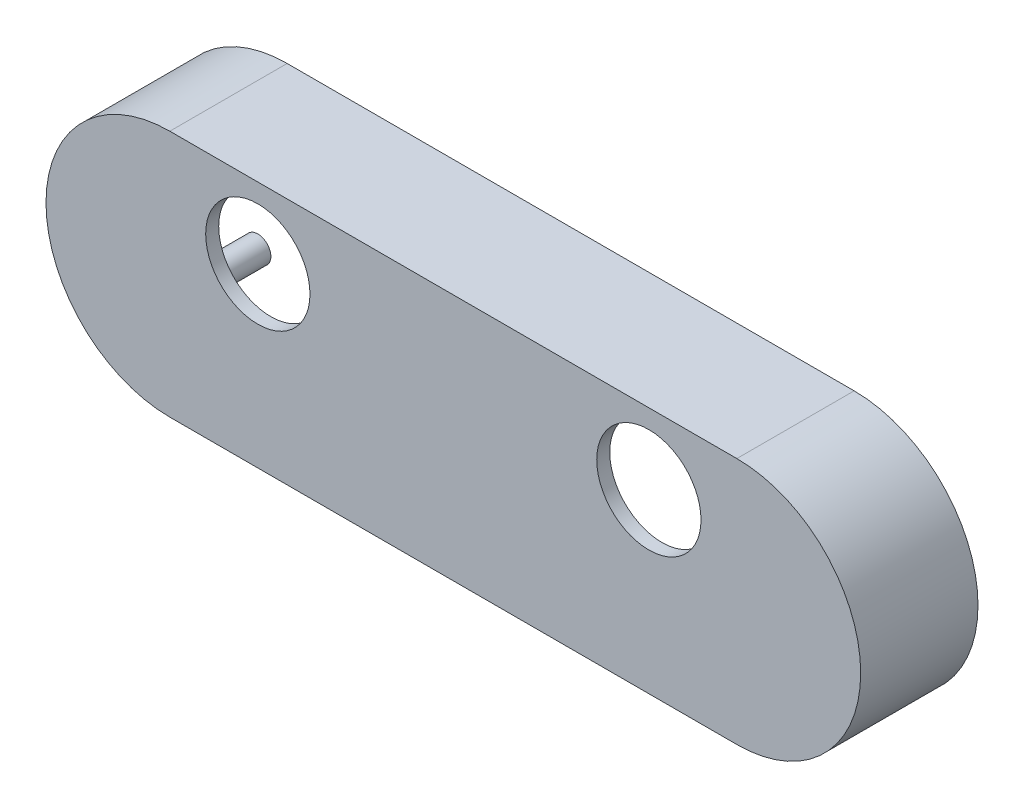
SolidWorks part; units mm, degrees
ref_plane "Front Plane" through (0, 0, 0) normal (0, 0, 1) x (1, 0, 0)
ref_plane "Top Plane" through (0, 0, 0) normal (0, 1, 0) x (1, 0, 0)
ref_plane "Right Plane" through (0, 0, 0) normal (1, 0, 0) x (0, 0, -1)
sketch "Sketch1" plane through (0, 0, 0) normal (0, 0, 1) x (1, 0, 0)
  line L0 (-43.5, 19) -> (43.5, 19)
  line L1 (-43.5, 17) -> (43.5, 17)
  line L3 (-43.5, -17) -> (43.5, -17)
  line L5 (-43.5, 17) -> (43.5, -17) construction
  line L6 (-43.5, -17) -> (43.5, 17) construction
  line L7 (-43.5, -19) -> (43.5, -19)
  line L8 (-43.5, 19) -> (43.5, -19) construction
  line L9 (-43.5, -19) -> (43.5, 19) construction
  arc A0 (-43.5, 17) -> (-43.5, -17) centre (-43.5, 0) ccw
  arc A1 (43.5, -17) -> (43.5, 17) centre (43.5, 0) ccw
  arc A2 (-43.5, 19) -> (-43.5, -19) centre (-43.5, 0) ccw
  arc A3 (43.5, -19) -> (43.5, 19) centre (43.5, 0) ccw
  point P0 (0, 0)
  point P7 (0, 0)
  point P15 (34.6361, -23.9977)
  point P16 (0, 0)
  dimension "D2" = 17
  dimension "D4" = 19
  dimension "D1" = 87
  dimension "D3" = 87
extrude "Boss-Extrude1" add sketch "Sketch1" along normal blind 2 contours L7 A3 L0 A2 A1 L3 A0 L1 | L1 A1 L3 A0 region at (0, 17.6935, 0)
extrude "Boss-Extrude2" add sketch "Sketch1<3>" against normal blind 16
sketch "Sketch1<3>" plane through (0, 0, 0) normal (0, 0, 1) x (1, 0, 0) same geometry as "Sketch1"
sketch "Sketch2" plane through (0, 0, 0) normal (0, 0, -1) x (-1, 0, 0)
  line L0 (-43.5, 17) -> (43.5, 17) construction
  circle A0 centre (-40, 15.1) radius 1
  circle A1 centre (-40, 15.1) radius 2
  circle A2 centre (-10, 15.1) radius 1
  circle A3 centre (-10, 15.1) radius 2
  circle A4 centre (-40, 0.1) radius 1
  circle A5 centre (-40, 0.1) radius 2
  circle A6 centre (-10, 0.1) radius 1
  circle A7 centre (-10, 0.1) radius 2
  circle A8 centre (10, 15.1) radius 1
  circle A9 centre (10, 15.1) radius 2
  circle A10 centre (40, 15.1) radius 1
  circle A11 centre (40, 15.1) radius 2
  circle A12 centre (10, 0.1) radius 1
  circle A13 centre (10, 0.1) radius 2
  circle A14 centre (40, 0.1) radius 1
  circle A15 centre (40, 0.1) radius 2
  point P20 (-40, 15.1)
  dimension "D1" = 2
  dimension "D2" = 4
  dimension "D5" = 2
  dimension "D6" = 4
  dimension "D3" = 15
  dimension "D4" = 30
  dimension "D7" = 30
  dimension "D8" = 15
  dimension "D9" = 20
  dimension "D10" = 10
  dimension "D11" = 1.9
extrude "Boss-Extrude3" add sketch "Sketch2" along normal blind 8
sketch "Sketch3" plane through (0, 0, 0) normal (0, 0, -1) x (-1, 0, 0)
  line L0 (-39.3755, 17) -> (-10.6245, 17) construction
  circle A0 centre (30, 8.1) radius 8
  circle A1 centre (-30, 8.1) radius 8
  point P4 (0, 0)
  point P6 (0, 0)
  dimension "D1" = 16
  dimension "D2" = 60
  dimension "D3" = 30
  dimension "D4" = 8.9
extrude "Cut-Extrude1" cut sketch "Sketch3" against normal blind 8
sketch "Sketch4" plane through (0, -19, 0) normal (0, -1, 0) x (1, 0, 0)
  line L0 (-43.5, 2) -> (43.5, 2) construction
  line L1 (-25.75, -13.45) -> (-12.75, -13.45)
  line L2 (-25.75, -13.45) -> (-25.75, -9.45)
  line L3 (-25.75, -9.45) -> (-12.75, -9.45)
  line L4 (-12.75, -13.45) -> (-12.75, -9.45)
  line L5 (-25.75, -13.45) -> (-12.75, -9.45) construction
  line L6 (-25.75, -9.45) -> (-12.75, -13.45) construction
  line L7 (-27, -14.9) -> (-11.5, -14.9)
  line L8 (-27, -14.9) -> (-27, -8)
  line L9 (-27, -8) -> (-11.5, -8)
  line L10 (-11.5, -14.9) -> (-11.5, -8)
  line L11 (-27, -14.9) -> (-11.5, -8) construction
  line L12 (-27, -8) -> (-11.5, -14.9) construction
  line L13 (12.75, -13.45) -> (25.75, -13.45)
  line L14 (12.75, -13.45) -> (12.75, -9.45)
  line L15 (12.75, -9.45) -> (25.75, -9.45)
  line L16 (25.75, -13.45) -> (25.75, -9.45)
  line L17 (12.75, -13.45) -> (25.75, -9.45) construction
  line L18 (12.75, -9.45) -> (25.75, -13.45) construction
  line L19 (11.5, -14.9) -> (27, -14.9)
  line L20 (11.5, -14.9) -> (11.5, -8)
  line L21 (11.5, -8) -> (27, -8)
  line L22 (27, -14.9) -> (27, -8)
  line L23 (11.5, -14.9) -> (27, -8) construction
  line L24 (11.5, -8) -> (27, -14.9) construction
  line L28 (11.5, -11.45) -> (-11.5, -11.45) construction
  circle A0 centre (0, -11.45) radius 4
  point P0 (-19.25, -11.45)
  point P5 (-19.25, -11.45)
  point P12 (0, 0)
  point P13 (19.25, -11.45)
  point P18 (19.25, -11.45)
  point P23 (0, 2)
  point P26 (0, 0)
  point P27 (-11.5, -11.45)
  dimension "D12" = 8
  dimension "D1" = 15.5
  dimension "D2" = 13
  dimension "D3" = 4
  dimension "D4" = 6.9
  dimension "D5" = 15.5
  dimension "10" = 10
  dimension "D6" = 13
  dimension "D7" = 4
  dimension "D8" = 6.9
  dimension "D9" = 10
  dimension "D10" = 23
  dimension "D11" = 11.5
extrude "Boss-Extrude4" add sketch "Sketch4" along normal blind 8 contours L19 L22 L21 L20 | L13 L16 L15 L14 | L8 L7 L10 L9 | L2 L1 L4 L3
extrude "Cut-Extrude2" cut sketch "Sketch4<2>" against normal blind 8 contours L13 L16 L15 L14 | L1 L4 L3 L2 | A0 region at (-19.25, -19, -11.45) region at (19.25, -19, -11.45)
sketch "Sketch4<2>" plane through (0, -19, 0) normal (0, -1, 0) x (1, 0, 0) same geometry as "Sketch4"
